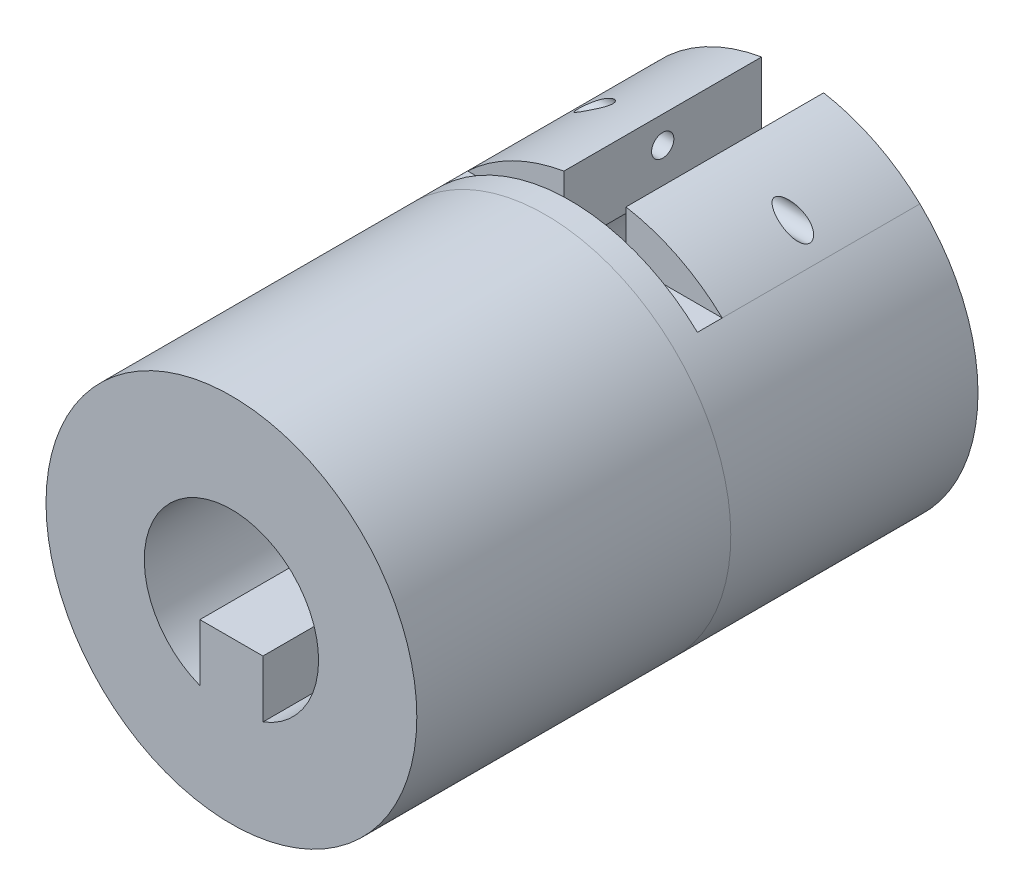
SolidWorks part; units mm, degrees
ref_plane "Front Plane" through (0, 0, 0) normal (0, 0, 1) x (1, 0, 0)
ref_plane "Top Plane" through (0, 0, 0) normal (0, 1, 0) x (1, 0, 0)
ref_plane "Right Plane" through (0, 0, 0) normal (1, 0, 0) x (0, 0, -1)
sketch "Sketch1" plane through (0, 0, 0) normal (0, 0, 1) x (1, 0, 0)
  line L1 (-2.5639, -12.8541) -> (2.5361, -12.8541)
  line L7 (2.5361, -17.4768) -> (2.5361, -12.8541)
  line L9 (-2.5639, -12.8541) -> (-2.5639, -17.4768)
  line L10 (-0.0139, -12.8541) -> (-0.0139, -17.9541) construction
  line L11 (-0.0139, -10.9041) -> (14.9861, -10.9041) construction
  line L12 (-0.0139, -10.9041) -> (-0.0139, -12.8541) construction
  circle A0 centre (-0.0139, -10.9041) radius 15
  circle A10 centre (-0.0139, -10.9041) radius 7.05
  arc A11 (-2.5639, -17.4768) -> (2.5361, -17.4768) centre (-0.0139, -10.9041) ccw
  dimension "D1" = 30
  dimension "D3" = 5.1
  dimension "D4" = 5.1
  dimension "D2" = 14.1
extrude "Boss-Extrude2" add sketch "Sketch1" along normal blind 25.4 contours A0 | L1 L7 A11 L9 | A10
sketch "Sketch11" plane through (0, 0, 0) normal (0, 0, -1) x (-1, 0, 0)
  circle A0 centre (0.0139, -10.9041) radius 0.0583
  circle A1 centre (0.0139, -10.9041) radius 15.0001
  circle A4 centre (0.0139, -10.9041) radius 15 construction
  circle A5 centre (0.0139, -10.9041) radius 15 construction
  point P0 (0.2526, -10.9041)
  dimension "D1" = 30.0002
extrude "Boss-Extrude3" add sketch "Sketch11" along normal blind 2 contours A1
sketch "Sketch12" plane through (0, 0, -2) normal (0, 0, -1) x (-1, 0, 0)
  line L0 (-2.4972, 3.8843) -> (2.5249, 3.8843) construction
  line L2 (2.5249, -1.5865) -> (2.5249, 3.8843)
  line L4 (-2.4972, 3.8843) -> (-2.4972, -1.5865)
  line L6 (0.0139, 3.8843) -> (0.0139, -10.9041) construction
  arc A0 (-2.4972, -1.5865) -> (2.5249, -1.5865) centre (0.0139, -10.9041) ccw
  circle A1 centre (0.0139, -10.9041) radius 15.0001 construction
  arc A2 (-2.4972, 3.8843) -> (2.5249, 3.8843) centre (0.0139, -10.9041) cw
  arc A3 (2.5249, 3.8843) -> (-2.4972, 3.8843) centre (0.0139, -10.9041) cw
  circle M5 centre (0.0139, -10.9041) radius 15.0001
  dimension "D1" = 19.3
  dimension "D3" = 15.0001
  dimension "D2" = 5.0221
extrude "Boss-Extrude4" add sketch "Sketch12" along normal blind 18 contours A0 L4 L2 M5 region at (-2.9477, 1.1489, -2)
sketch "Sketch13" plane through (0, 0, 0) normal (0, 1, 0) x (1, 0, 0)
  line L0 (-15.014, 20) -> (-15.014, 0) construction
  line L1 (-15.014, 2) -> (14.9863, 2)
  line L2 (-15.014, 2) -> (-15.014, 4.0078)
  line L3 (-15.014, 4.0078) -> (14.9863, 4.0078)
  line L4 (14.9863, 2) -> (14.9863, 4.0078)
  line L5 (14.9863, 0) -> (14.9863, 20) construction
extrude "Cut-Extrude1" cut sketch "Sketch13" along normal blind 22 contours L3 L4 L1 L2
sketch "Sketch14" plane through (0, 0, 0) normal (1, 0, 0) x (0, 0, -1)
  line L0 (4.0078, 3.8843) -> (20, 3.8843) construction
  line L1 (20, 3.8843) -> (12.0039, 3.8843) construction
  line L2 (12.0039, 3.8843) -> (12.0039, 1.6938) construction
  circle A0 centre (12.0039, 1.6938) radius 0.9
  dimension "D1" = 1.8
  dimension "D2" = 2.1905
extrude "Cut-Extrude2" cut sketch "Sketch14" against normal through all both and the other way through all
